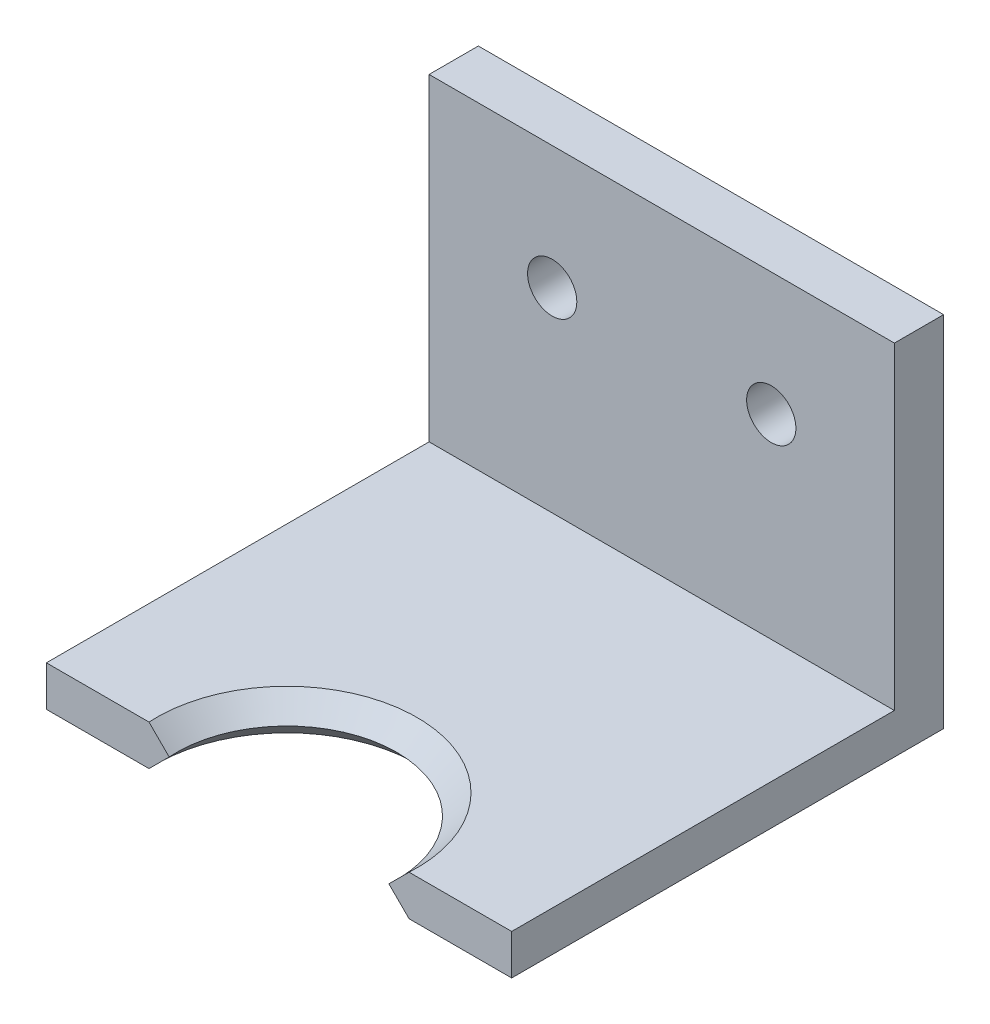
SolidWorks part; units mm, degrees
ref_plane "Front Plane" through (0, 0, 0) normal (0, 0, 1) x (1, 0, 0)
ref_plane "Top Plane" through (0, 0, 0) normal (0, 1, 0) x (1, 0, 0)
ref_plane "Right Plane" through (0, 0, 0) normal (1, 0, 0) x (0, 0, -1)
sketch "Profile-Sketch1" plane through (0, 0, 0) normal (1, 0, 0) x (0, 0, -1)
  line L0 (0, 0) -> (24.675, 0)
  line L1 (24.675, 0) -> (24.675, 20.5151)
  line L2 (24.675, 20.5151) -> (27.85, 20.5151)
  line L3 (27.85, 20.5151) -> (27.85, -2.6)
  line L4 (27.85, -2.6) -> (0, -2.6)
  line L5 (0, -2.6) -> (0, 0)
  dimension "D1" = 3.175
  dimension "D2" = 27.85
  dimension "D3" = 23.1151
  dimension "D4" = 2.6
extrude "Profile-Boss-Extrude1" add sketch "Profile-Sketch1" along normal blind 30
sketch "CollarSketch2" plane through (0, 0, 0) normal (0, 1, 0) x (1, 0, 0)
  line L0 (30, 0) -> (0, 0) construction
  line L1 (0, 24.675) -> (0, 0) construction
  line L2 (7.9176, 0) -> (22.0824, 0)
  arc A0 (22.0824, 0) -> (7.9176, 0) centre (15, 0.5) ccw
  dimension "D1" = 14.2
  dimension "D2" = 0.5
  dimension "D3" = 15
extrude "CollarCut-Extrude1" cut sketch "CollarSketch2" against normal through all
chamfer "Collar-Chamfer2" distance 1.3 angle 45 2 edges at (15, -2.6, -7.6) (15, 0, -7.6)
sketch "MountingHoles-Sketch3" plane through (0, 0, -24.675) normal (0, 0, 1) x (1, 0, 0)
  line L0 (30, 20.5151) -> (0, 20.5151) construction
  line L1 (30, 20.5151) -> (30, 0) construction
  line L2 (0, 20.5151) -> (0, 0) construction
  circle A12 centre (7.9375, 12.5776) radius 1.5875
  circle A13 centre (22.0625, 12.5776) radius 1.5875
  dimension "D4" = 3.175
  dimension "D1" = 7.9375
  dimension "D2" = 7.9375
  dimension "D3" = 7.9375
extrude "MountingHoles-Cut-Extrude2" cut sketch "MountingHoles-Sketch3" against normal through all
equation "\"RailThickness\"= .125in'Spec"
equation "\"D1@Profile-Sketch1\"=\"RailThickness\""
equation "\"LM8UUCollarDiameter\"= 14.2mm"
equation "\"LM8UUDiameter\"= 15mm"
equation "\"MidSideRailHeight\"= 1.25in"
equation "\"RodStabilizerWidth\"= \"StepperMountingHoleOffsetFromLeftOrRightSide\" + \"StepperMountingHoleDistance\" / 2 + \"RailThickness\" - \"RodStabilizerCollarOffset\" + 1mm"
equation "\"RodStabilizerDepth\"= \"LM8UUDiameter\" * 2"
equation "\"D2@Profile-Sketch1\" = \"RodStabilizerWidth\""
equation "\"D3@Profile-Sketch1\" = \"RodStabilizerLength\""
equation "\"D1@Profile-Boss-Extrude1\" = \"RodStabilizerDepth\""
equation "\"D1@CollarSketch2\" = \"LM8UUCollarDiameter\""
equation "\"D3@CollarSketch2\" = \"RodStabilizerDepth\" / 2"
equation "\"HoleOffsetFromEdge\"= \"RailThickness\" * 2.5"
equation "\"StepperMountingHoleOffsetFromItsSide\"= 5.5mm'Spec"
equation "\"StepperMountingHoleOffsetFromLeftOrRightSide\"= \"StepperMountingHoleOffsetFromItsSide\" + \"RailThickness\""
equation "\"StepperMountingHoleDistance\"= 31mm'Spec"
equation "\"RodStabilizerCollarOffset\"= 0.5mm"
equation "\"D2@CollarSketch2\"=\"RodStabilizerCollarOffset\""
equation "\"LM8UUHeight\"= 24mm'Spec"
equation "\"ZAxisLeadScrewLength\"= 200mm"
equation "\"LM8UUEndToStartOfCollar\"= 2.5mm"
equation "\"LegHeight\"= 70mm'Space needed for PSU/Stepper/Electronics"
equation "\"V1 BottomOfLowerRail\"= \"LegHeight\""
equation "\"LM8UUCollarWidth\"= 1.3mm"
equation "\"StepperShaftLength\"= 24mm'Pulley will be attached to the end"
equation "\"V2 ToBedAtTopOfZAxis\"= \"V1 BottomOfLowerRail\" + \"StepperShaftLength\" + \"ZAxisLeadScrewLength\" - \"LM8UUHeight\" / 2"
equation "\"HotEndToTopOfXAxisGB\"= 63.315144mm'Measured from the100.Should be 63.315144"
equation "\"TopOfGBToBottomOfLinearRail\"= \"LinearGBWidth\" / 2 + \"LinearRailWidth\" / 2"
equation "\"LinearGBWidth\"= 27mm'Spec"
equation "\"V5 ToBottomOfXAxisLinearRail\"= \"V4 ToTopOfBuildPlate/HotEndTip\" + \"HotEndToTopOfXAxisGB\" - \"TopOfGBToBottomOfLinearRail\""
equation "\"LinearRailWidth\"= 12mm'Spec"
equation "\"V6 ToBottomOfGantryPulley\"= \"V5 ToBottomOfXAxisLinearRail\" - \"DistanceFromGABTopToLowerPulley\""
equation "\"GABUpperHeight\"= 6mm"
equation "\"GABMidWallHeight\"= 28mm'Must equal 28 or changes alignment"
equation "\"20TGT2PulleyWidth\"= 8.7mm'The STL of the Pulley in the diagram is a bit larger"
equation "\"GABMidShortRiserHeight\"= \"GABMidWallHeight\" / 2 - \"20TGT2PulleyWidth\"'Equals 5.3"
equation "\"GABRiserBossOffset\"= 0.8mm'Aligns Pulleys"
equation "\"DistanceFromGABTopToLowerPulley\"= \"GABUpperHeight\" + \"GABMidWallHeight\" - \"GABMidShortRiserHeight\" + \"GABRiserBossOffset\" / 2"
equation "\"V7 ToTopOfMidBackRail\"= \"V6 ToBottomOfGantryPulley\" + \"StepperShaftLength\""
equation "\"BedToBuildPlateStandoffLength\"= 15mm"
equation "\"BuildPlateHeight\"= 8mm'Spec"
equation "\"V4 ToTopOfBuildPlate/HotEndTip\"= \"V2 ToBedAtTopOfZAxis\" + \"BedToBuildPlateStandoffLength\" + \"BuildPlateHeight\""
equation "\"D1@MountingHoles-Sketch3\"=\"HoleOffsetFromEdge\""
equation "\"D2@MountingHoles-Sketch3\"=\"HoleOffsetFromEdge\""
equation "\"D3@MountingHoles-Sketch3\"=\"HoleOffsetFromEdge\""
equation "\"FasteningHoleDiameter\"= .125in"
equation "\"D4@MountingHoles-Sketch3\"=\"FasteningHoleDiameter\""
equation "\"D4@Profile-Sketch1\"=\"LM8UUCollarWidth\"*2"
equation "\"RodStabilizerLength\"= \"V7 ToTopOfMidBackRail\" - \"RailThickness\" - \"MidSideRailHeight\" - \"V2 ToBedAtTopOfZAxis\" - \"LM8UUHeight\" + \"HoleOffsetFromEdge\" * 2 + \"LM8UUEndToStartOfCollar\" + \"LM8UUCollarWidth\" / 2 + \"LM8UUCollarWidth\"'Equals 23.11514"
equation "\"D1@Collar-Chamfer2\"=\"LM8UUCollarWidth\""
